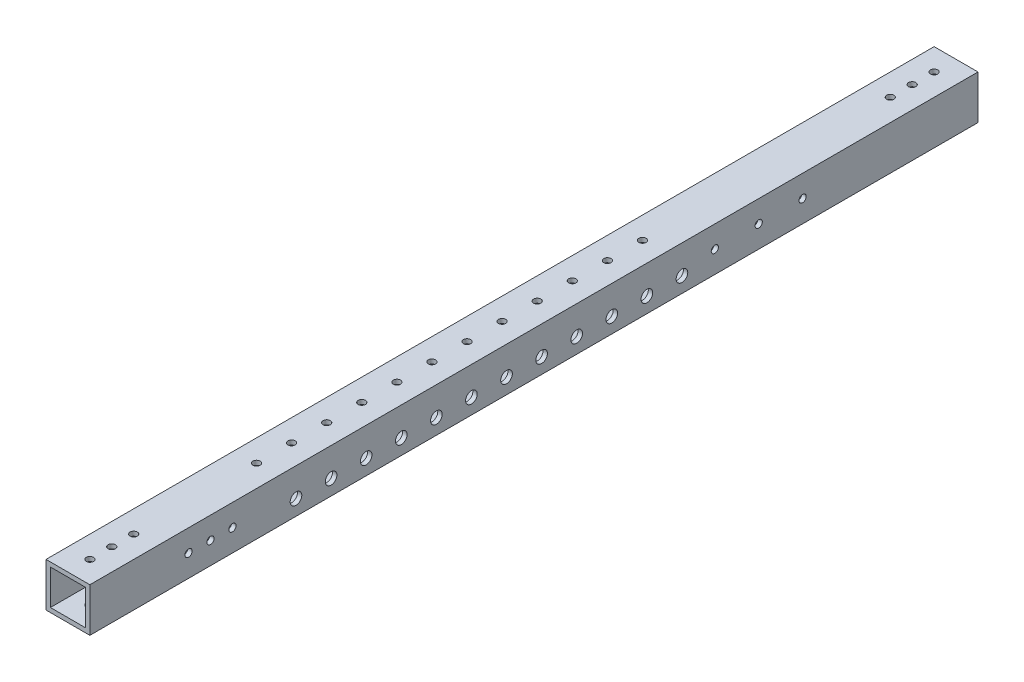
SolidWorks part; units mm, degrees
ref_plane "前视基准面" through (0, 0, 0) normal (0, 0, 1) x (1, 0, 0)
ref_plane "上视基准面" through (0, 0, 0) normal (0, 1, 0) x (1, 0, 0)
ref_plane "右视基准面" through (0, 0, 0) normal (1, 0, 0) x (0, 0, -1)
other "Configuration Table"
sketch "草图1" plane through (0, 0, 0) normal (0, 0, 1) x (1, 0, 0)
  line L1 (-8, -8) -> (8, -8)
  line L2 (-8, -8) -> (-8, 8)
  line L3 (-8, 8) -> (8, 8)
  line L4 (8, -8) -> (8, 8)
  line L5 (-8, -8) -> (8, 8) construction
  line L6 (-8, 8) -> (8, -8) construction
  line L7 (-10, -10) -> (10, -10)
  line L8 (-10, -10) -> (-10, 10)
  line L9 (-10, 10) -> (10, 10)
  line L10 (10, -10) -> (10, 10)
  line L11 (-10, -10) -> (10, 10) construction
  line L12 (-10, 10) -> (10, -10) construction
  point P0 (0, 0)
  point P6 (0, 0)
  dimension "D1" = 20
  dimension "D2" = 20
  dimension "D3" = 2
  dimension "D4" = 2
extrude "凸台-拉伸1" add sketch "草图1" along normal blind 405
sketch "草图2" plane through (0, 0, 0) normal (0, 1, 0) x (1, 0, 0)
  line L0 (0, 0) -> (0, -405) construction
  line L1 (10, -405) -> (-10, -405) construction
  circle A0 centre (0, -395) radius 1.65
  circle A1 centre (0, -385) radius 1.65
  circle A2 centre (0, -375) radius 1.65
  dimension "D1" = 3.3
  dimension "D3" = 3.3
  dimension "D4" = 3.3
  dimension "D2" = 10
  dimension "D5" = 10
  dimension "D6" = 10
extrude "切除-拉伸1" cut sketch "草图2" against normal mid plane 20
sketch "草图4" plane through (0, 0, 0) normal (0, 1, 0) x (1, 0, 0)
  line L0 (-10, -10) -> (10, -10) construction
  line L1 (-10, -405) -> (-10, 0) construction
  line L2 (10, -405) -> (10, 0) construction
  line L3 (10, 0) -> (-10, 0) construction
  circle A0 centre (0, -10) radius 1.65
  circle A1 centre (0, -20) radius 1.65
  circle A2 centre (0, -30) radius 1.65
  dimension "D2" = 3.3
  dimension "D3" = 3.3
  dimension "D4" = 3.3
  dimension "D1" = 10
  dimension "D5" = 10
  dimension "D6" = 20
extrude "切除-拉伸3" cut sketch "草图4" against normal mid plane 20
sketch "草图10" plane through (10, 0, 0) normal (1, 0, 0) x (0, 0, -1)
  line L0 (0, -10) -> (0, 10) construction
  line L1 (-135, -3) -> (-327, -3) construction
  line L2 (-405, 10) -> (0, 10) construction
  circle A0 centre (-120, 0) radius 1.65
  circle A1 centre (-100, 0) radius 1.65
  circle A2 centre (-80, 0) radius 1.65
  circle A3 centre (-135, -3) radius 2.65
  circle A4 centre (-151, -3) radius 2.65
  circle A5 centre (-167, -3) radius 2.65
  circle A6 centre (-183, -3) radius 2.65
  circle A7 centre (-199, -3) radius 2.65
  circle A8 centre (-215, -3) radius 2.65
  circle A9 centre (-231, -3) radius 2.65
  circle A10 centre (-247, -3) radius 2.65
  circle A11 centre (-263, -3) radius 2.65
  circle A12 centre (-279, -3) radius 2.65
  circle A13 centre (-295, -3) radius 2.65
  circle A14 centre (-311, -3) radius 2.65
  circle A17 centre (-327, -3) radius 2.65 [skipped]
  circle A18 centre (-360, 0) radius 1.65
  circle A19 centre (-350, 0) radius 1.65
  circle A20 centre (-340, 0) radius 1.65
  dimension "D1" = 3.3
  dimension "D3" = 3.3
  dimension "D4" = 3.3
  dimension "D7" = 5.3
  dimension "D12" = 3.3
  dimension "D2" = 120
  dimension "D5" = 20
  dimension "D6" = 20
  dimension "D8" = 15
  dimension "D10" = 13
  dimension "D11" = 360
  dimension "D13" = 10
  dimension "D9" = 13
  dimension "D14" = 3
extrude "切除-拉伸4" cut sketch "草图10" against normal through all
sketch "草图11" plane through (0, 10, 0) normal (0, 1, 0) x (1, 0, 0)
  line L0 (0, 0) -> (0, -143) construction
  circle A0 centre (0, -143) radius 1.65
  circle A1 centre (0, -159) radius 1.65
  circle A2 centre (0, -175) radius 1.65
  circle A3 centre (0, -191) radius 1.65
  circle A4 centre (0, -207) radius 1.65
  circle A5 centre (0, -223) radius 1.65
  circle A6 centre (0, -239) radius 1.65
  circle A7 centre (0, -255) radius 1.65
  circle A8 centre (0, -271) radius 1.65
  circle A9 centre (0, -287) radius 1.65
  circle A10 centre (0, -303) radius 1.65
  circle A11 centre (0, -319) radius 1.65
  dimension "D2" = 3.3
  dimension "D1" = 143
  dimension "D3" = 12
extrude "切除-拉伸5" cut sketch "草图11" against normal through all
